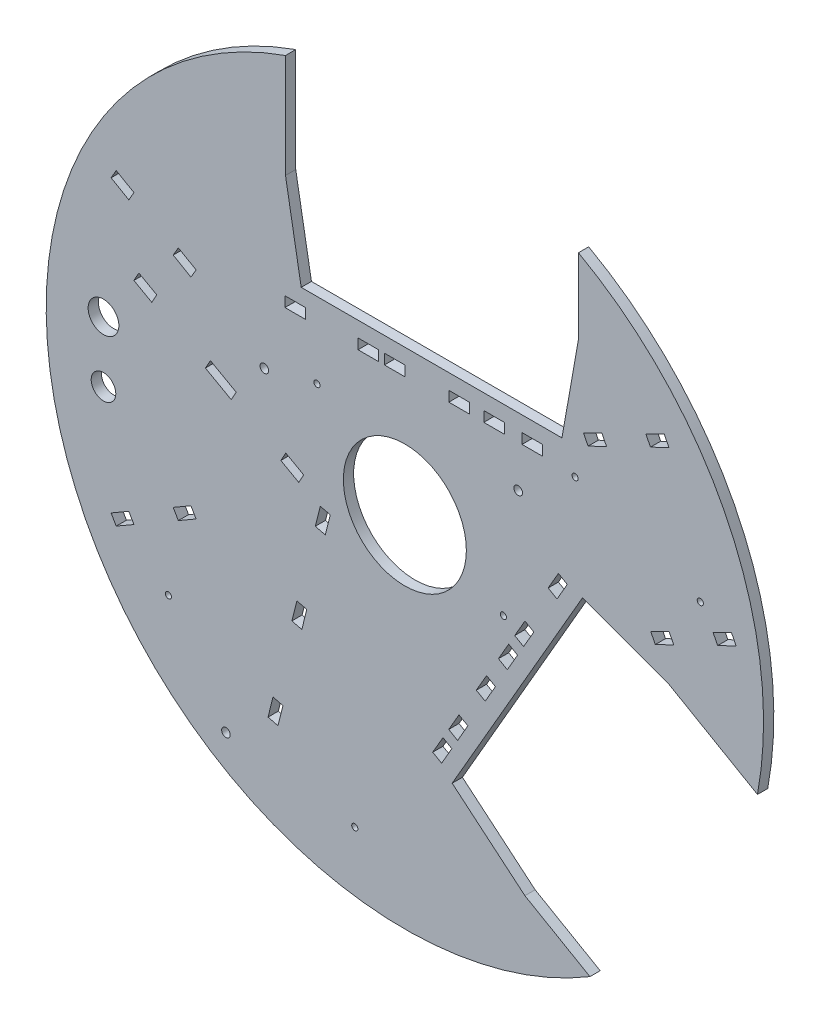
SolidWorks part; units mm, degrees
material "Balsa"
ref_plane "Plan de face" through (0, 0, 0) normal (0, 0, 1) x (1, 0, 0)
ref_plane "Plan de dessus" through (0, 0, 0) normal (0, 1, 0) x (1, 0, 0)
ref_plane "Plan de droite" through (0, 0, 0) normal (1, 0, 0) x (0, 0, -1)
sketch "Esquisse1" plane through (0, 0, 0) normal (0, 0, 1) x (1, 0, 0)
  circle A0 centre (0, 0) radius 175
  dimension "D1" = 350
extrude "Boss.-Extru.1" add sketch "Esquisse1" along normal blind 5
sketch "Esquisse2" plane through (0, 0, 0) normal (0, 0, -1) x (-1, 0, 0)
  line L0 (58.2408, 114.332) -> (58.2408, 213.8766)
  line L1 (58.2408, 213.8766) -> (-84.6817, 213.8766)
  line L2 (-84.6817, 213.8766) -> (-84.6817, 116.5135)
  line L3 (0, 0) -> (-290.6498, 0) construction
  line L4 (-84.6817, 116.5135) -> (-76.6366, 70.8876)
  line L5 (-76.6366, 70.8876) -> (50.5804, 70.8876)
  line L6 (50.5804, 70.8876) -> (58.2408, 114.332)
  line L7 (-128.1349, -6.728) -> (-214.343, -56.5003)
  line L8 (-214.343, -56.5003) -> (-142.8818, -180.2748)
  line L9 (-142.8818, -180.2748) -> (-58.5628, -131.5932)
  line L10 (-58.5628, -131.5932) -> (-23.0722, -101.8131)
  line L11 (-23.0722, -101.8131) -> (-86.6807, 8.3601)
  line L12 (-86.6807, 8.3601) -> (-128.1349, -6.728)
  point P16 (0, 0)
  point P43 (0, 0)
  dimension "D5" = 142.989
  dimension "D6" = 99.5446
  dimension "D1" = 127.217
  dimension "D2" = 100
  dimension "D3" = 100
  dimension "D4" = 142.9225
  dimension "D7" = 70.8876
  dimension "D8" = 50.5804
  dimension "D10" = 120
  dimension "D9" = 2
extrude "Enlèv. mat.-Extru.1" cut sketch "Esquisse2" against normal blind 5
sketch "Esquisse3" plane through (0, 0, 5) normal (0, 0, 1) x (1, 0, 0)
  line L0 (0, 0) -> (0, 103.8673) construction
  line L1 (-49.3567, -7.7578) -> (-58.0775, -2.8643)
  line L2 (-49.3567, -7.7578) -> (-51.8034, -12.1183)
  line L3 (-58.0775, -2.8643) -> (-60.5243, -7.2247)
  line L4 (-51.8034, -12.1183) -> (-60.5243, -7.2247)
  line L5 (-82.2991, 10.7274) -> (-94.8707, 17.7817)
  line L6 (-82.2991, 10.7274) -> (-84.7459, 6.3669)
  line L7 (-94.8707, 17.7817) -> (-97.3175, 13.4213)
  line L8 (-84.7459, 6.3669) -> (-97.3175, 13.4213)
  line L9 (-121.0332, 32.4625) -> (-129.754, 37.356)
  line L10 (-121.0332, 32.4625) -> (-123.48, 28.1021)
  line L11 (-129.754, 37.356) -> (-132.2008, 32.9956)
  line L12 (-123.48, 28.1021) -> (-132.2008, 32.9956)
  line L13 (-36.4119, -18.1392) -> (-38.8398, -27.84)
  line L14 (-36.4119, -18.1392) -> (-41.2623, -16.9253)
  line L15 (-38.8398, -27.84) -> (-43.6902, -26.6261)
  line L16 (0, 0) -> (104.6701, 42.2895) construction
  line L17 (-41.2623, -16.9253) -> (-43.6902, -26.6261)
  line L18 (-47.8487, -63.8364) -> (-50.2765, -73.5372)
  line L19 (-47.8487, -63.8364) -> (-52.6991, -62.6224)
  line L20 (-50.2765, -73.5372) -> (-55.1269, -72.3233)
  line L21 (-52.6991, -62.6224) -> (-55.1269, -72.3233)
  line L22 (-59.4765, -110.2968) -> (-61.9044, -119.9976)
  line L23 (-59.4765, -110.2968) -> (-64.3269, -109.0829)
  line L24 (-61.9044, -119.9976) -> (-66.7548, -118.7837)
  line L25 (-64.3269, -109.0829) -> (-66.7548, -118.7837)
  line L26 (62.9144, -18.0042) -> (58.5843, -15.5042)
  line L27 (62.9144, -18.0042) -> (57.9144, -26.6645)
  line L28 (58.5843, -15.5042) -> (53.5843, -24.1645)
  line L29 (57.9144, -26.6645) -> (53.5843, -24.1645)
  line L30 (39.8511, -47.9511) -> (44.1813, -50.4511)
  line L31 (39.8511, -47.9511) -> (34.8511, -56.6113)
  line L32 (44.1813, -50.4511) -> (39.1813, -59.1113)
  line L33 (34.8511, -56.6113) -> (39.1813, -59.1113)
  line L34 (18.5843, -84.7863) -> (22.9144, -87.2863)
  line L35 (18.5843, -84.7863) -> (13.5843, -93.4465)
  line L36 (22.9144, -87.2863) -> (17.9144, -95.9465)
  line L37 (13.5843, -93.4465) -> (17.9144, -95.9465)
  line L38 (23.0722, -101.8131) -> (86.6807, 8.3601) construction
  line L40 (67.1551, 63.3876) -> (57.1551, 63.3876)
  line L41 (67.1551, 63.3876) -> (67.1551, 58.3876)
  line L42 (67.1551, 58.3876) -> (57.1551, 58.3876)
  line L43 (57.1551, 63.3876) -> (57.1551, 58.3876)
  line L44 (-12.8449, 63.3876) -> (-22.8449, 63.3876)
  line L45 (-12.8449, 63.3876) -> (-12.8449, 58.3876)
  line L46 (-12.8449, 58.3876) -> (-22.8449, 58.3876)
  line L47 (-22.8449, 63.3876) -> (-22.8449, 58.3876)
  line L48 (31.4441, 63.3876) -> (21.4441, 63.3876)
  line L49 (31.4441, 63.3876) -> (31.4441, 58.3876)
  line L50 (31.4441, 58.3876) -> (21.4441, 58.3876)
  line L51 (21.4441, 63.3876) -> (21.4441, 58.3876)
  line L52 (76.6366, 70.8876) -> (-50.5804, 70.8876) construction
  line B0 (122.1484, 6.3102) -> (119.9636, 10.8076)
  line B1 (128.9584, 15.1772) -> (119.9636, 10.8076)
  line B2 (131.1432, 10.6797) -> (122.1484, 6.3102)
  line B3 (131.1432, 10.6797) -> (128.9584, 15.1772)
  line B4 (159.3791, 29.9551) -> (150.3842, 25.5855)
  line B5 (152.569, 21.0881) -> (150.3842, 25.5855)
  line B6 (161.5639, 25.4577) -> (159.3791, 29.9551)
  line B7 (161.5639, 25.4577) -> (152.569, 21.0881)
  line B8 (126.6073, 97.4163) -> (117.6125, 93.0467)
  line B9 (126.6073, 97.4163) -> (128.7921, 92.9189)
  line B10 (117.6125, 93.0467) -> (119.7973, 88.5493)
  line B11 (128.7921, 92.9189) -> (119.7973, 88.5493)
  line B12 (96.1867, 82.6383) -> (98.3714, 78.1409)
  line B13 (96.1867, 82.6383) -> (87.1918, 78.2688)
  line B14 (98.3714, 78.1409) -> (89.3766, 73.7714)
  line B15 (87.1918, 78.2688) -> (89.3766, 73.7714)
  line B16 (87.1918, 78.2688) -> (104.6701, 42.2895) construction
  dimension "D1" = 112.6276
  dimension "D2" = 68
  dimension "D3" = 5
  dimension "D4" = 5
  dimension "D5" = 30.9185
  dimension "D6" = 7.4
  dimension "D7" = 5
  dimension "D8" = 10
  dimension "D9" = 10
  dimension "D10" = 10
  dimension "D11" = 10
  dimension "D12" = 5
  dimension "D13" = 10
  dimension "D14" = 32.5336
  dimension "D15" = 10
  dimension "D16" = 27.4664
  dimension "D17" = 7.5
  dimension "D18" = 10
sketch_block_instance "Bloc1-1"
sketch_block "Bloc1" parameters "D1"=5, "D2"=23.8202, "D3"=40, "D4"=10, "D5"=10, "D6"=5
extrude "Enlèv. mat.-Extru.2" cut sketch "Esquisse3" against normal blind 10
sketch "Esquisse4" plane through (0, 0, 0) normal (0, 0, -1) x (-1, 0, 0)
  line L0 (42.8627, 33.9844) -> (-48.07, -18.5156) construction
  line L1 (42.8627, 33.9844) -> (115.3627, -91.5893) construction
  line L2 (-48.07, -18.5156) -> (24.43, -144.0893) construction
  line L3 (115.3627, -91.5893) -> (24.43, -144.0893) construction
  line L4 (-23.0722, -101.8131) -> (-86.6807, 8.3601) construction
  circle A0 centre (115.3627, -91.5893) radius 1.5
  circle A1 centre (24.43, -144.0893) radius 1.5
  circle A2 centre (-48.07, -18.5156) radius 1.5
  circle A3 centre (42.8627, 33.9844) radius 1.5
  dimension "D1" = 3
  dimension "D2" = 105
  dimension "D3" = 145
  dimension "D4" = 20
  dimension "D5" = 8
extrude "Enlèv. mat.-Extru.3" cut sketch "Esquisse4" against normal blind 10
sketch "Esquisse5" plane through (0, 0, 0) normal (0, 0, -1) x (-1, 0, 0)
  line L0 (132.1784, -70.1252) -> (134.6784, -65.7951)
  line L1 (132.1784, -70.1252) -> (140.8387, -75.1252)
  line L2 (134.6784, -65.7951) -> (143.3387, -70.7951)
  line L3 (140.8387, -75.1252) -> (143.3387, -70.7951)
  line L4 (110.5278, -57.6252) -> (113.0278, -53.2951)
  line L5 (110.5278, -57.6252) -> (101.8675, -52.6252)
  line L6 (113.0278, -53.2951) -> (104.3675, -48.2951)
  line L7 (101.8675, -52.6252) -> (104.3675, -48.2951)
  line L8 (134.6784, 65.7951) -> (132.1784, 70.1252)
  line L9 (134.6784, 65.7951) -> (143.3387, 70.7951)
  line L10 (132.1784, 70.1252) -> (140.8387, 75.1252)
  line L11 (143.3387, 70.7951) -> (140.8387, 75.1252)
  line L12 (110.5278, 57.6252) -> (113.0278, 53.2951)
  line L13 (110.5278, 57.6252) -> (101.8675, 52.6252)
  line L14 (113.0278, 53.2951) -> (104.3675, 48.2951)
  line L15 (101.8675, 52.6252) -> (104.3675, 48.2951)
  line L16 (134.6784, 65.7951) -> (113.0278, 53.2951) construction
  line L17 (143.3387, 70.7951) -> (104.3675, 48.2951) construction
  line L18 (143.3387, -70.7951) -> (104.3675, -48.2951) construction
  dimension "D1" = 10
  dimension "D2" = 115
  dimension "D3" = 25
  dimension "D4" = 25
  dimension "D5" = 5
  dimension "D6" = 115
extrude "Enlèv. mat.-Extru.4" cut sketch "Esquisse5" against normal blind 10
sketch "Esquisse6" plane through (0, 0, 5) normal (0, 0, 1) x (1, 0, 0)
  line L0 (20.7319, -91.0665) -> (84.2319, 18.9187) construction
  line L1 (25.7319, -82.4063) -> (30.7319, -73.746)
  line L2 (25.7319, -82.4063) -> (21.4018, -79.9063)
  line L3 (30.7319, -73.746) -> (26.4018, -71.246)
  line L4 (21.4018, -79.9063) -> (26.4018, -71.246)
  line L5 (49.9819, -40.4041) -> (54.9819, -31.7438)
  line L6 (49.9819, -40.4041) -> (45.6518, -37.9041)
  line L7 (54.9819, -31.7438) -> (50.6518, -29.2438)
  line L8 (45.6518, -37.9041) -> (50.6518, -29.2438)
  line L9 (52.4819, -36.0739) -> (43.8216, -31.0739) construction
  line L10 (58.5, 63.3876) -> (-68.5, 63.3876) construction
  line L11 (48.5, 63.3876) -> (38.5, 63.3876)
  line L12 (48.5, 63.3876) -> (48.5, 58.3876)
  line L14 (74.9018, 12.7584) -> (69.9018, 4.0982)
  line L15 (74.2319, 1.5982) -> (69.9018, 4.0982)
  line L16 (79.2319, 10.2584) -> (74.9018, 12.7584)
  line L17 (79.2319, 10.2584) -> (74.2319, 1.5982)
  line L20 (57.9144, -26.6645) -> (62.9144, -18.0042) construction
  line L21 (38.5, 63.3876) -> (38.5, 58.3876)
  line L22 (48.5, 58.3876) -> (38.5, 58.3876)
  line L23 (0, 63.3876) -> (-10, 63.3876)
  line L24 (0, 63.3876) -> (0, 58.3876)
  line L25 (-10, 63.3876) -> (-10, 58.3876)
  line L26 (0, 58.3876) -> (-10, 58.3876)
  line L27 (-5, 63.3876) -> (-5, 53.3876) construction
  line L29 (-58.5, 58.3876) -> (-48.5, 58.3876)
  line L30 (-48.5, 63.3876) -> (-48.5, 58.3876)
  line L31 (-58.5, 63.3876) -> (-58.5, 58.3876)
  line L32 (-58.5, 63.3876) -> (-48.5, 63.3876)
  line L33 (67.1551, 63.3876) -> (57.1551, 63.3876) construction
  dimension "D1" = 127
  dimension "D2" = 10
  dimension "D3" = 10
  dimension "D4" = 5
  dimension "D5" = 5
  dimension "D6" = 10
  dimension "D7" = 127
  dimension "D8" = 10
  dimension "D9" = 10
  dimension "D10" = 5
  dimension "D11" = 10
  dimension "D12" = 5
extrude "Enlèv. mat.-Extru.5" cut sketch "Esquisse6" against normal blind 5
hole_wizard "Trou taraudé M51" positions "Esquisse8" profile "Esquisse9" tap size "M5" standard "ISO" end condition through all
sketch "Esquisse8" plane through (0, 0, -85) normal (0, 0, -1) x (1, 0, 0)
  point P0 (-68.569, -27.6625)
  point P2 (55.2809, -37.9834)
  point P4 (-87.2993, 135.5593)
sketch "Esquisse9" plane through (-68.569, 27.6625, -85) normal (1, 0, 0) x (0, 1, 0)
  line L0 (0, 0) -> (0, 90)
  line L1 (0, 90) -> (2.1, 90)
  line L2 (2.1, 90) -> (2.1, 0)
  line L3 (2.1, 0) -> (0, 0)
  line L4 (0, -6.35) -> (0, 107.95) construction
  dimension "Diamètre principal du filetage" = 4.2
  dimension "Profondeur du trou pour taraudage jusqu'au prochain" = 90
sketch "Esquisse10" plane through (0, 0, 5) normal (0, 0, 1) x (1, 0, 0)
  circle A0 centre (0, 0) radius 30
  circle A1 centre (-147.0421, -19.3351) radius 6
  circle A2 centre (-147.0421, 10.1871) radius 7.5
extrude "Enlèv. mat.-Extru.6" cut sketch "Esquisse10" against normal blind 5
sketch "Esquisse11" plane through (0, 0, 0) normal (0, 0, -1) x (-1, 0, 0)
  line L0 (-66.1598, 24.3425) -> (-135.6971, -0.967) construction
  line L1 (-66.1598, 24.3425) -> (-91.4693, 93.8798) construction
  line L2 (-135.6971, -0.967) -> (-161.0066, 68.5703) construction
  line L3 (-91.4693, 93.8798) -> (-161.0066, 68.5703) construction
  line L4 (-66.1598, 24.3425) -> (-161.0066, 68.5703) construction
  line L5 (-135.6971, -0.967) -> (-91.4693, 93.8798) construction
  line L6 (-144.1232, 35.3407) -> (-83.0432, 57.572) construction
  line L7 (-86.6807, 8.3601) -> (-128.1349, -6.728) construction
  circle A0 centre (-144.1232, 35.3407) radius 1.5
  circle A1 centre (-83.0432, 57.572) radius 1.5
  arc A2 (-84.6817, 153.147) -> (-172.0356, -32.0741) centre (0, 0) ccw construction
  point P1 (-113.5832, 46.4564)
  dimension "D3" = 3
  dimension "D1" = 74
  dimension "D2" = 65
  dimension "D4" = 32.5
  dimension "D5" = 8
extrude "Enlèv. mat.-Extru.7" cut sketch "Esquisse11" against normal blind 10
